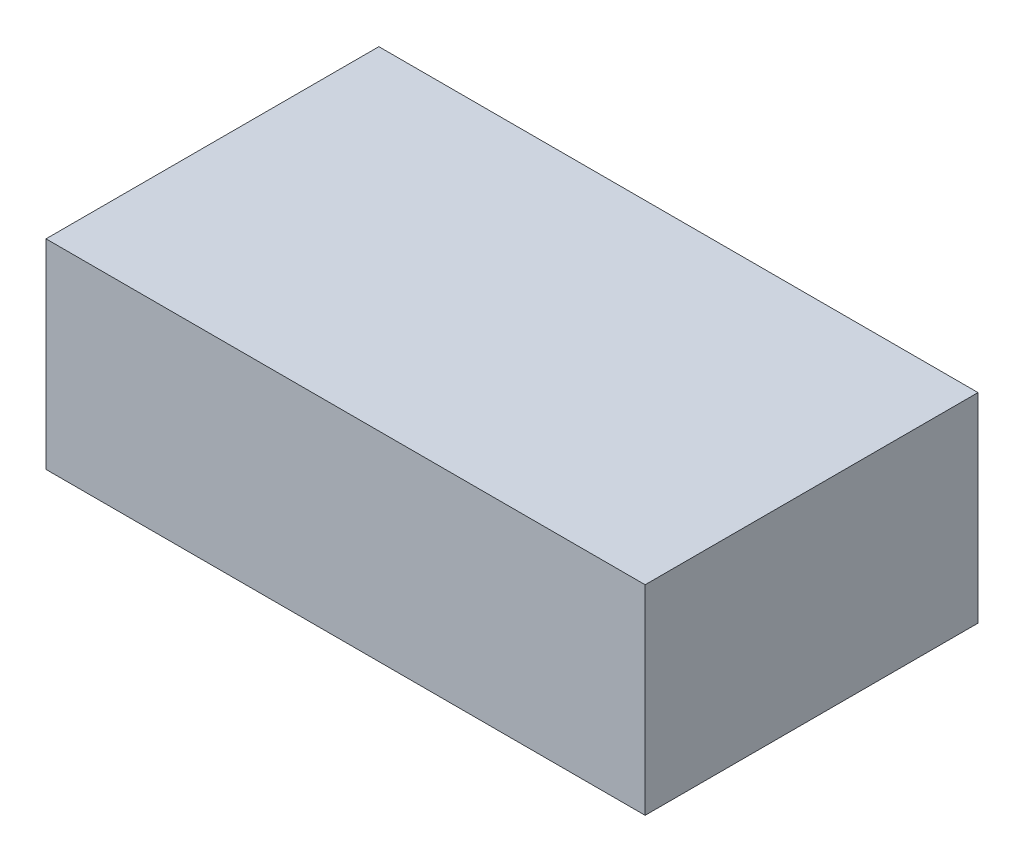
SolidWorks part; units mm, degrees
ref_plane "Спереди" through (0, 0, 0) normal (0, 0, 1) x (1, 0, 0)
ref_plane "Сверху" through (0, 0, 0) normal (0, 1, 0) x (1, 0, 0)
ref_plane "Справа" through (0, 0, 0) normal (1, 0, 0) x (0, 0, -1)
sketch "Эскиз1" plane through (0, 0, 0) normal (0, 1, 0) x (1, 0, 0)
  line L1 (-90, 50) -> (90, 50)
  line L2 (-90, 50) -> (-90, -50)
  line L3 (-90, -50) -> (90, -50)
  line L4 (90, 50) -> (90, -50)
  line L5 (-90, 50) -> (90, -50) construction
  line L6 (-90, -50) -> (90, 50) construction
  point P0 (0, 0)
extrude "Бобышка-Вытянуть1" add sketch "Эскиз1" along normal blind 60
